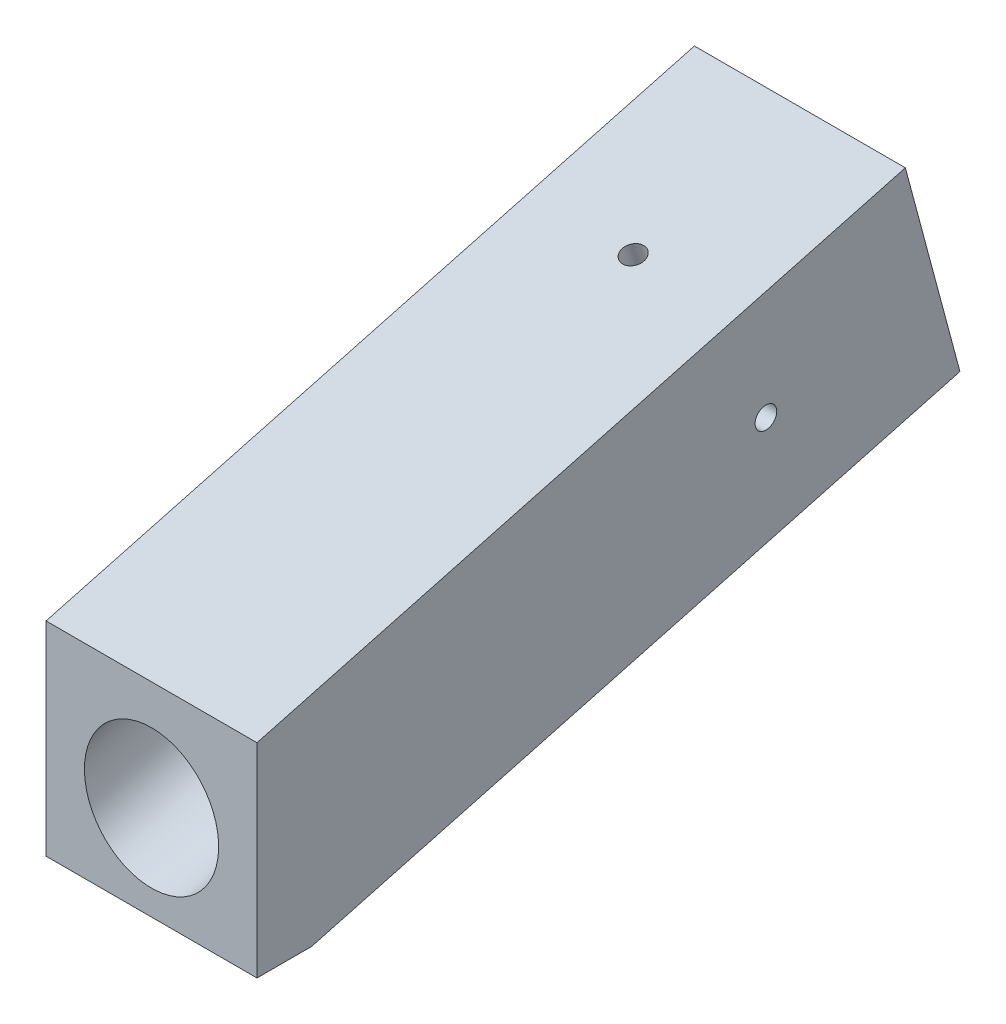
SolidWorks part; units mm, degrees
ref_plane "Front Plane" through (0, 0, 0) normal (0, 0, 1) x (1, 0, 0)
ref_plane "Top Plane" through (0, 0, 0) normal (0, 1, 0) x (1, 0, 0)
ref_plane "Right Plane" through (0, 0, 0) normal (1, 0, 0) x (0, 0, -1)
sketch "Sketch1" plane through (0, 0, 0) normal (1, 0, 0) x (0, 0, -1)
  line L0 (-30.9604, -19.6839) -> (36.6544, -1.5665)
  line L1 (-30.9604, -19.6839) -> (-36.6544, 1.5665)
  line L2 (36.6544, -1.5665) -> (30.9604, 19.6839)
  line L3 (-36.6544, 1.5665) -> (30.9604, 19.6839)
  line L4 (-30.9604, -19.6839) -> (30.9604, 19.6839) construction
  line L5 (36.6544, -1.5665) -> (-36.6544, 1.5665) construction
  line L6 (0, 0) -> (43.4864, 0) construction
  line L7 (-33.8074, -9.0587) -> (33.8074, 9.0587) construction
  point P1 (0, 0)
  dimension "D1" = 15
  dimension "D2" = 22
  dimension "D3" = 70
extrude "Boss-Extrude1" add sketch "Sketch1" along normal blind 11 and the other way blind 11
sketch "Sketch5" plane through (11, 0, 0) normal (1, 0, 0) x (0, 0, -1)
  line L0 (-36.6544, 1.5665) -> (-36.6544, -19.6839)
  line L1 (-36.6544, -19.6839) -> (-30.9604, -19.6839)
  line L2 (-30.9604, -19.6839) -> (-36.6544, 1.5665)
extrude "Boss-Extrude2" add sketch "Sketch5" against normal up to surface (22 mm away) up to face at (-11, 0, 0)
sketch "Sketch2" plane through (0, 9.0587, -33.8074) normal (0, 0.2588, -0.9659) x (-1, 0, 0)
  circle A0 centre (0, 0) radius 7
  dimension "D1" = 14
extrude "Cut-Extrude1" cut sketch "Sketch2" against normal through all
sketch "Sketch3" plane through (0, -10.6252, -2.847) normal (0, -0.9659, -0.2588) x (1, 0, 0)
  line L0 (-11, -35) -> (11, -35) construction
  line L1 (0, -35) -> (0, -27) construction
  circle A0 centre (0, -27) radius 1.1303
  dimension "D1" = 2.2606
  dimension "D2" = 8
extrude "Cut-Extrude2" cut sketch "Sketch3" against normal up to next
ref_axis "Axis1" through (0, -8.1039, 30.244) along (0, 0.2588, -0.9659)
sketch "Sketch4" plane through (11, 0, 0) normal (1, 0, 0) x (0, 0, -1)
  line L0 (36.6544, -1.5665) -> (30.9604, 19.6839) construction
  line L1 (16.4207, 4.3999) -> (33.8074, 9.0587) construction
  line L2 (-30.9604, -19.6839) -> (36.6544, -1.5665) construction
  circle A0 centre (16.4207, 4.3999) radius 1.1303
  dimension "D2" = 2.2606
  dimension "D1" = 18
extrude "Cut-Extrude3" cut sketch "Sketch4" against normal up to next
pattern_circular "CirPattern1" count 3 over 180 about axis through (0, -8.1039, 30.244) along (0, 0.2588, -0.9659) of "Cut-Extrude3" reverse direction yes
